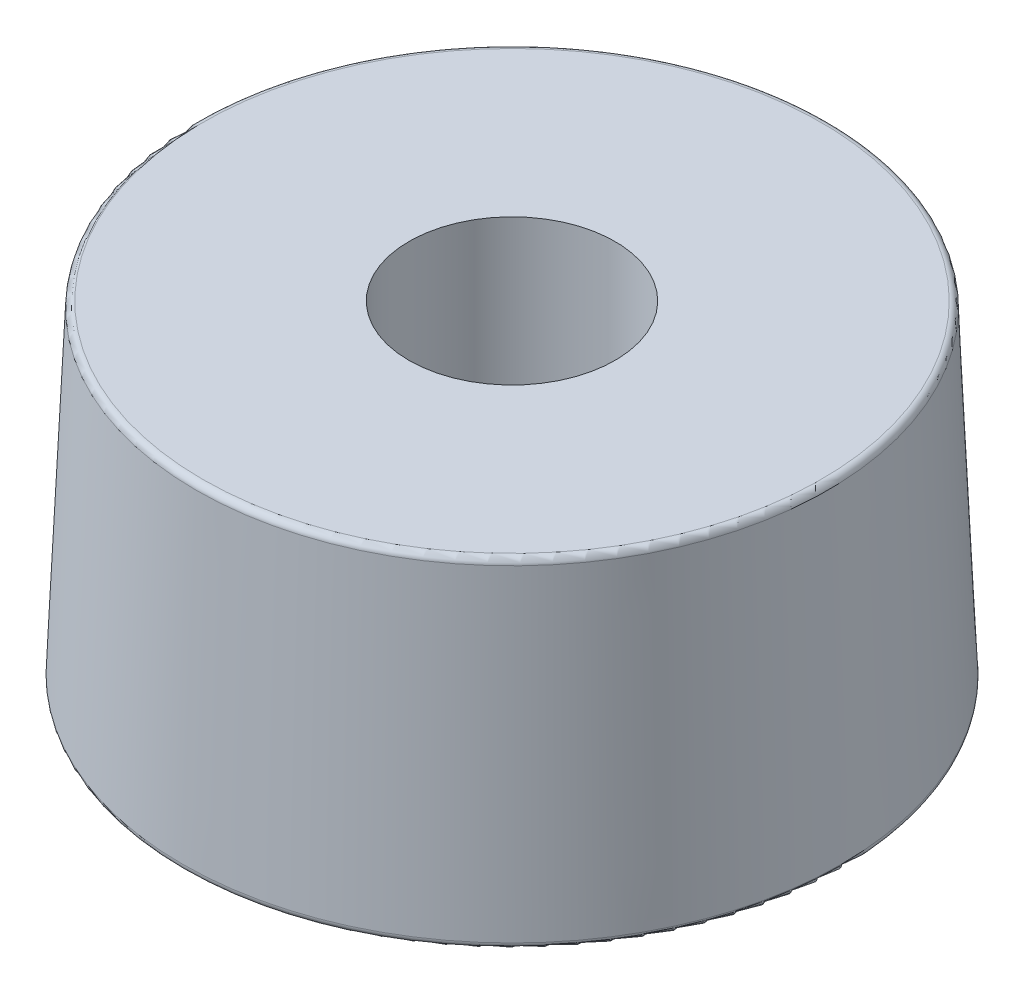
SolidWorks part; units mm, degrees
material "Zinc AG40A (Zn-4Al-0.4Mg; Zamak 3), Cast"
ref_plane "Front Plane" through (0, 0, 0) normal (0, 0, 1) x (1, 0, 0)
ref_plane "Top Plane" through (0, 0, 0) normal (0, 1, 0) x (1, 0, 0)
ref_plane "Right Plane" through (0, 0, 0) normal (1, 0, 0) x (0, 0, -1)
sketch "Sketch1" plane through (0, 0, 0) normal (0, 1, 0) x (1, 0, 0)
  circle A0 centre (0, 0) radius 25.4
  circle A1 centre (0, 0) radius 7.9375
  dimension "D1" = 15.875
  dimension "D2" = 50.8
extrude "Boss-Extrude1" add sketch "Sketch1" along normal mid plane 25.4
chamfer "Chamfer1" distance 25.4 angle 2.5 1 edges at (0, 12.7, 25.4) first distance on face at (0, 12.7, 25.4)
fillet "Fillet1" radius 0.5 2 edges at (0, 12.7, 24.291) (0, -12.7, 25.4)
